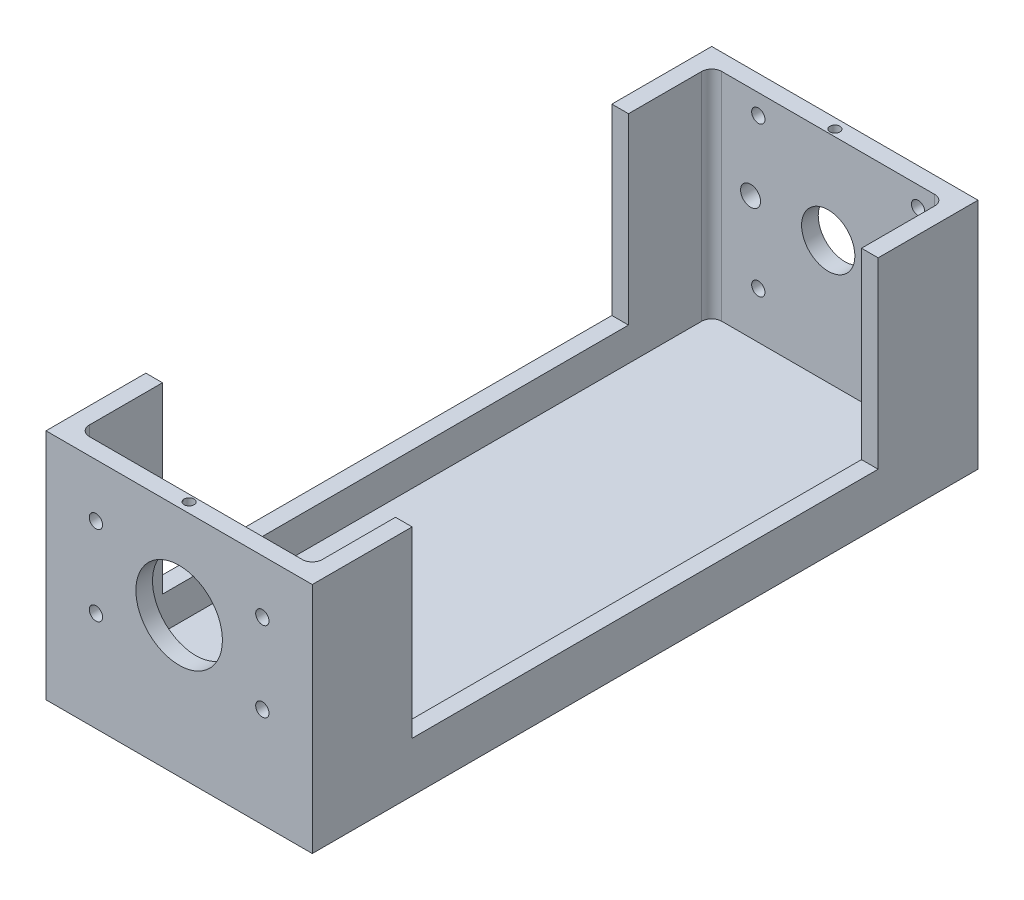
SolidWorks part; units mm, degrees
ref_plane "前视基准面" through (0, 0, 0) normal (0, 0, 1) x (1, 0, 0)
ref_plane "上视基准面" through (0, 0, 0) normal (0, 1, 0) x (1, 0, 0)
ref_plane "右视基准面" through (0, 0, 0) normal (1, 0, 0) x (0, 0, -1)
sketch "草图1" plane through (0, 0, 0) normal (0, 0, 1) x (1, 0, 0)
  line L1 (-40, -35) -> (40, -35)
  line L2 (-40, -35) -> (-40, 35)
  line L3 (-40, 35) -> (40, 35)
  line L4 (40, -35) -> (40, 35)
  line L5 (-40, -35) -> (40, 35) construction
  line L6 (-40, 35) -> (40, -35) construction
  point P0 (0, 0)
  dimension "D1" = 80
  dimension "D2" = 70
extrude "凸台-拉伸1" add sketch "草图1" against normal blind 200
sketch "草图2" plane through (0, 35, 0) normal (0, 1, 0) x (1, 0, 0)
  line L0 (-35, 192) -> (-35, 8)
  line L1 (-32, 5) -> (32, 5)
  line L2 (35, 8) -> (35, 192)
  line L3 (32, 195) -> (-32, 195)
  line L4 (-40, 0) -> (40, 0)
  line L5 (40, 0) -> (40, 200)
  line L6 (40, 200) -> (-40, 200)
  line L7 (-40, 200) -> (-40, 0)
  line L8 (-40, 0) -> (40, 0)
  line L9 (40, 0) -> (40, 200)
  line L10 (40, 200) -> (-40, 200)
  line L11 (-40, 200) -> (-40, 0)
  line L12 (-35, 5) -> (35, 5) construction
  line L13 (35, 5) -> (35, 195) construction
  line L14 (-35, 195) -> (-35, 5) construction
  line L15 (35, 195) -> (-35, 195) construction
  arc A0 (32, 5) -> (35, 8) centre (32, 8) ccw
  arc A1 (-35, 8) -> (-32, 5) centre (-32, 8) ccw
  arc A2 (35, 192) -> (32, 195) centre (32, 192) ccw
  arc A3 (-35, 192) -> (-32, 195) centre (-32, 192) cw
  dimension "D3" = 3
  dimension "D1" = 0
  dimension "D2" = 5
extrude "切除-拉伸1" cut sketch "草图2" against normal blind 65 contours A3 L0 A1 L1 A0 L2 A2 L3 region at (0, 35, -100)
sketch "草图3" plane through (0, 0, 0) normal (0, 0, 1) x (1, 0, 0)
  line L0 (0, 0) -> (0, 37.0041) construction
  line L1 (-40, -29) -> (40, -29) construction
  line L2 (-40, 35) -> (-40, -35) construction
  line L3 (40, -35) -> (40, 35) construction
  line L4 (-40, -35) -> (40, -35) construction
  line L5 (40, 35) -> (-40, 35) construction
  line L6 (-34, -29) -> (40, -29) construction
  line L9 (0, 7) -> (0, 35) construction
  line L10 (-26, 7) -> (26, 7) construction
  circle A0 centre (-26, 7) radius 3.5 construction
  circle A1 centre (0, 7) radius 13
  circle A2 centre (26, 7) radius 3.5 construction
  dimension "D2" = 7
  dimension "D3" = 26
  dimension "D4" = 7
  dimension "D1" = 6
  dimension "D5" = 28
  dimension "D6" = 26
  dimension "D7" = 26
extrude "切除-拉伸2" cut sketch "草图3" against normal blind 10
sketch "草图4" plane through (-40, 0, 0) normal (-1, 0, 0) x (0, 0, 1)
  line L0 (-126.5, -4) -> (-153.5, -4)
  line L1 (-126.5, -4) -> (-126.5, 32)
  line L2 (-126.5, 32) -> (-153.5, 32)
  line L3 (-153.5, -4) -> (-153.5, 32)
  line L4 (-140, -1.9135) -> (-140, 22.4271) construction
  line L5 (-200, 35) -> (0, 35) construction
  line L6 (-200, 35) -> (-200, -35) construction
  circle A0 centre (-121.5, 2) radius 2
  circle A1 centre (-121.5, 26) radius 2
  circle A2 centre (-158.5, 26) radius 2
  circle A3 centre (-158.5, 2) radius 2
  dimension "D1" = 4
  dimension "D2" = 4
  dimension "D3" = 36
  dimension "D4" = 6
  dimension "D5" = 5
  dimension "D6" = 6
  dimension "D7" = 5
  dimension "D8" = 27
  dimension "D9" = 3
  dimension "D10" = 60
extrude "切除-拉伸3" cut sketch "草图4" against normal blind 10
sketch "草图6" plane through (0, -30, 0) normal (0, 1, 0) x (1, 0, 0)
  line L0 (-17, 114) -> (-17, 167) construction
  line L1 (-17, 140.5) -> (-23.7867, 140.5) construction
  line L2 (-35, 192) -> (-35, 8) construction
  line L3 (32, 195) -> (-32, 195) construction
  circle A0 centre (-17, 167) radius 3.5
  circle A1 centre (-17, 114) radius 3.5
  dimension "D2" = 7
  dimension "D5" = 7
  dimension "D1" = 53
  dimension "D3" = 18
  dimension "D4" = 54.5
extrude "切除-拉伸5" [suppressed] cut sketch "草图6" against normal blind 10
sketch "草图7" plane through (0, 35, 0) normal (0, 1, 0) x (1, 0, 0)
  line L0 (0, -10.1016) -> (0, 210.5413) construction
  line L1 (40, 0) -> (-40, 0) construction
  line L2 (40, 200) -> (40, 0) construction
  line L3 (-40, 200) -> (-40, 0) construction
  line L4 (40, 200) -> (-40, 200) construction
  circle A0 centre (-37, 150) radius 1.5
  circle A1 centre (-37, 50) radius 1.5
  circle A2 centre (37, 50) radius 1.5
  circle A3 centre (37, 150) radius 1.5
  circle A4 centre (0, 197) radius 1.5
  circle A5 centre (0, 3) radius 1.5
  dimension "D1" = 100
  dimension "D3" = 50
  dimension "D5" = 3
  dimension "D6" = 3
  dimension "D7" = 3
  dimension "D8" = 3
  dimension "D9" = 3
  dimension "D10" = 3
  dimension "D11" = 3
  dimension "D12" = 3
  dimension "D14" = 3
  dimension "D15" = 3
  dimension "D16" = 3
  dimension "D2" = 100
  dimension "D4" = 50
  dimension "D13" = 3
extrude "切除-拉伸6" cut sketch "草图7" against normal blind 10
sketch "草图8" plane through (40, 0, 0) normal (1, 0, 0) x (0, 0, -1)
  line L0 (200, 35) -> (0, 35) construction
  line L1 (30, 35) -> (170, 35)
  line L2 (30, 35) -> (30, -20)
  line L3 (30, -20) -> (170, -20)
  line L4 (170, 35) -> (170, -20)
  line L5 (30, 35) -> (170, -20) construction
  line L6 (30, -20) -> (170, 35) construction
  line L7 (0, -35) -> (0, 35) construction
  dimension "D1" = 140
  dimension "D2" = 55
  dimension "D3" = 30
extrude "切除-拉伸7" cut sketch "草图8" against normal through all
sketch "草图9" plane through (0, 0, -5) normal (0, 0, -1) x (-1, 0, 0)
  circle A0 centre (-25, -5) radius 2 construction
  circle A1 centre (-25, 19) radius 2 construction
  circle A2 centre (25, 19) radius 2 construction
  circle A3 centre (25, -5) radius 2 construction
  circle A4 centre (-25, -5) radius 2
  circle A5 centre (-25, 19) radius 2
  circle A6 centre (25, 19) radius 2
  circle A7 centre (25, -5) radius 2
extrude "切除-拉伸8" cut sketch "草图9" against normal blind 6
sketch "草图10" plane through (0, 0, -200) normal (0, 0, -1) x (-1, 0, 0)
  circle A0 centre (0, 7) radius 13 construction
  circle A1 centre (0, 7) radius 13 construction
  circle A2 centre (0, 7) radius 8
  dimension "D1" = 16
extrude "切除-拉伸9" cut sketch "草图10" against normal blind 10
sketch "草图11" plane through (0, 0, -195) normal (0, 0, 1) x (1, 0, 0)
  circle A0 centre (-21, 29) radius 2 construction
  circle A1 centre (-21, -16) radius 2 construction
  circle A2 centre (-23.3281, 7) radius 3 construction
  circle A3 centre (27, 29) radius 2 construction
  circle A4 centre (24.6719, 7) radius 3 construction
  circle A5 centre (27, -16) radius 2 construction
  circle A6 centre (-21, 29) radius 2
  circle A7 centre (-21, -16) radius 2
  circle A8 centre (-23.3281, 7) radius 3
  circle A9 centre (27, 29) radius 2
  circle A10 centre (24.6719, 7) radius 3
  circle A11 centre (27, -16) radius 2
extrude "切除-拉伸10" cut sketch "草图11" against normal blind 6
